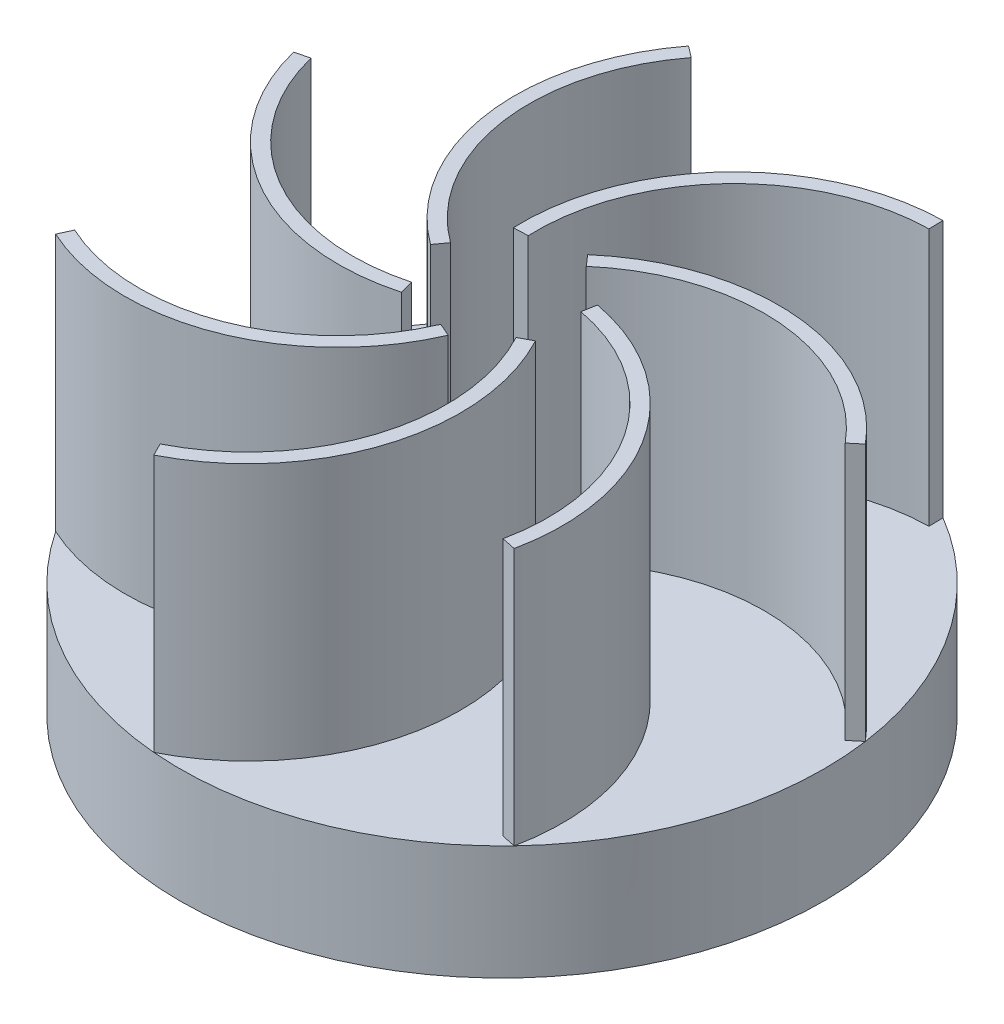
SolidWorks part; units mm, degrees
material "PTFE (general)"
ref_plane "Front Plane" through (0, 0, 0) normal (0, 0, 1) x (1, 0, 0)
ref_plane "Top Plane" through (0, 0, 0) normal (0, 1, 0) x (1, 0, 0)
ref_plane "Right Plane" through (0, 0, 0) normal (1, 0, 0) x (0, 0, -1)
sketch "Sketch1" plane through (0, 0, 0) normal (0, 1, 0) x (1, 0, 0)
  line L0 (0, 0) -> (17.0102, 14.7277) construction
  line L1 (0, 22.5) -> (0, -22.5) construction
  line L2 (-22.5, 0) -> (22.5, 0) construction
  line L3 (0, 0) -> (-17.0102, 14.7277) construction
  line L4 (0, 0) -> (17.0102, -14.7277) construction
  line L5 (0, 0) -> (-17.0102, -14.7277) construction
  circle A0 centre (0, 0) radius 22.5
  dimension "D1" = 45
extrude "Boss-Extrude1" add sketch "Sketch1" along normal blind 2
sketch "Sketch3" plane through (0, 2, 0) normal (0, 1, 0) x (1, 0, 0)
  circle A0 centre (0, 0) radius 5
  dimension "D1" = 10
extrude "Cut-Extrude3" cut sketch "Sketch3" against normal blind 10
sketch "Sketch4" plane through (0, 2, 0) normal (0, 1, 0) x (1, 0, 0)
  line L0 (-22.5, 0) -> (22.5, 0) construction
  line L1 (0, 22.5) -> (0, -22.5) construction
  circle A0 centre (0, 0) radius 22.5 construction
extrude "Boss-Extrude2" add sketch "Sketch4" along normal blind 6 contours L1 L0
sketch "Sketch5" plane through (0, 8, 0) normal (0, 1, 0) x (1, 0, 0)
  arc A0 (-5, 0) -> (-7.9934, 21.0323) centre (3.7849, 11.9794) cw
  circle A1 centre (0, 0) radius 5 construction
  circle A2 centre (0, 0) radius 22.5 construction
  arc A3 (-3.1174, 3.9092) -> (11.4599, 19.3629) centre (11.7257, 4.5099) cw
  arc A4 (1.1126, 4.8746) -> (22.2836, 3.1129) centre (10.8369, -6.3557) cw
  arc A5 (4.5048, 2.1694) -> (16.3273, -15.4812) centre (1.7876, -12.4353) cw
  arc A6 (4.5048, -2.1694) -> (-1.9238, -22.4176) centre (-8.6077, -9.1509) cw
  arc A7 (1.1126, -4.8746) -> (-18.7262, -12.4731) centre (-12.5213, 1.0243) cw
  arc A8 (-3.1174, -3.9092) -> (-21.4275, 6.8639) centre (-7.0061, 10.4282) cw
  point P37 (0, 0)
  dimension "D1" = 7
extrude "Extrude-Thin1" add sketch "Sketch5" along normal blind 18 thin
sketch "Sketch7" plane through (0, 8, 0) normal (0, 1, 0) x (1, 0, 0)
  circle A0 centre (0, 0) radius 5
  circle A1 centre (0, 0) radius 2.5
extrude "Boss-Extrude3" add sketch "Sketch7" against normal through all
